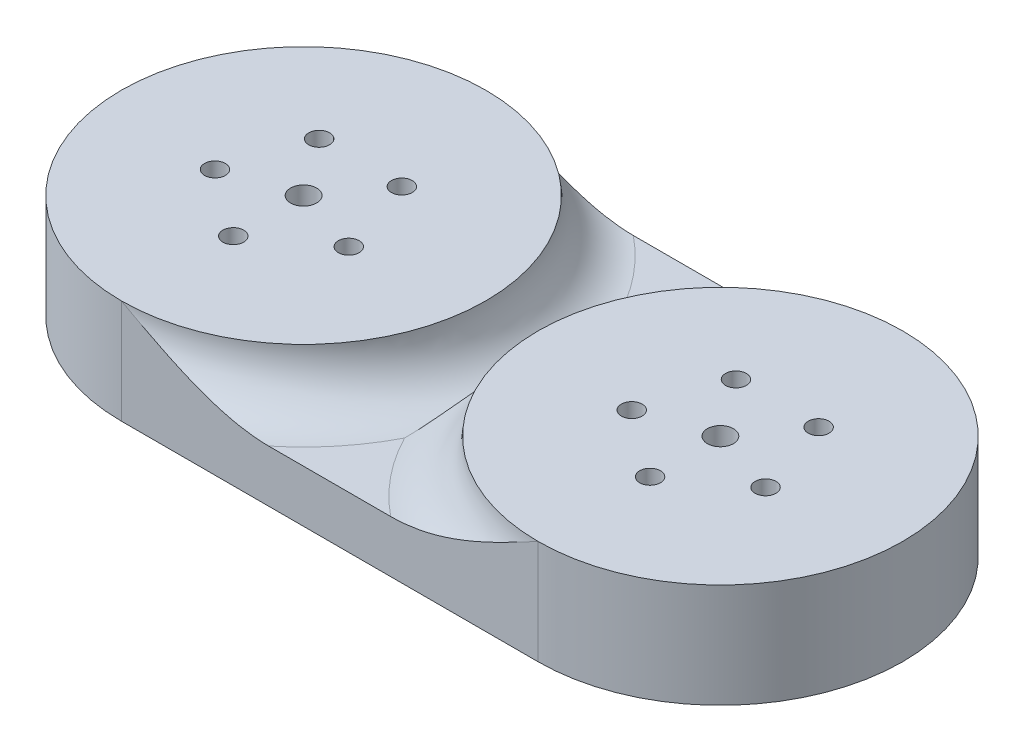
SolidWorks part; units mm, degrees
ref_plane "Front Plane" through (0, 0, 0) normal (0, 0, 1) x (1, 0, 0)
ref_plane "Top Plane" through (0, 0, 0) normal (0, 1, 0) x (1, 0, 0)
ref_plane "Right Plane" through (0, 0, 0) normal (1, 0, 0) x (0, 0, -1)
sketch "Sketch1" plane through (0, 0, 0) normal (0, 1, 0) x (1, 0, 0)
  circle A0 centre (0, 0) radius 35
  dimension "D1" = 70
extrude "Boss-Extrude1" add sketch "Sketch1" along normal blind 10
sketch "Sketch2" plane through (0, 0, 0) normal (0, -1, 0) x (1, 0, 0)
  circle A0 centre (0, 0) radius 13.5 construction
  circle A1 centre (0, 13.5) radius 2
  circle A2 centre (12.8393, 4.1717) radius 2
  circle A3 centre (7.9351, -10.9217) radius 2
  circle A4 centre (-7.9351, -10.9217) radius 2
  circle A5 centre (-12.8393, 4.1717) radius 2
  point P16 (0, 0)
  dimension "D1" = 27
  dimension "D2" = 4
extrude "Cut-Extrude1" cut sketch "Sketch2" against normal through all
sketch "Sketch3" plane through (0, 0, 0) normal (0, -1, 0) x (1, 0, 0)
  line L0 (0, 0) -> (80, 0) construction
  line L1 (80, 35) -> (0, 35)
  line L2 (80, -35) -> (0, -35)
  line L3 (40, 35) -> (40, -35) construction
  arc A0 (80, -35) -> (80, 35) centre (80, 0) ccw
  circle A1 centre (0, 0) radius 35 construction
  circle A2 centre (67.1607, 4.1717) radius 2
  circle A3 centre (0, 0) radius 35
  arc A4 (0, 35) -> (0, -35) centre (0, 0) ccw
  circle A5 centre (-12.8393, 4.1717) radius 2
  circle A6 centre (-12.8393, 4.1717) radius 2
  circle A7 centre (-7.9351, -10.9217) radius 2
  circle A8 centre (-7.9351, -10.9217) radius 2
  circle A9 centre (7.9351, -10.9217) radius 2
  circle A10 centre (7.9351, -10.9217) radius 2
  circle A11 centre (12.8393, 4.1717) radius 2
  circle A12 centre (12.8393, 4.1717) radius 2
  circle A13 centre (0, 13.5) radius 2
  circle A14 centre (0, 13.5) radius 2
  circle A15 centre (72.0649, -10.9217) radius 2
  circle A16 centre (87.9351, -10.9217) radius 2
  circle A17 centre (92.8393, 4.1717) radius 2
  circle A18 centre (80, 13.5) radius 2
  dimension "D1" = 80
  dimension "D2" = 0
  dimension "D3" = 0
  dimension "D4" = 0
  dimension "D5" = 0
  dimension "D6" = 0
  dimension "D7" = 0
extrude "Boss-Extrude2" add sketch "Sketch3" along normal blind 10
sketch "Sketch4" plane through (0, 0, 0) normal (0, 1, 0) x (1, 0, 0)
  circle A0 centre (80, 0) radius 35
  arc A1 (80, -35) -> (80, 35) centre (80, 0) ccw construction
  circle A2 centre (87.9351, 10.9217) radius 2 construction
  circle A3 centre (92.8393, -4.1717) radius 2 construction
  circle A4 centre (67.1607, -4.1717) radius 2 construction
  circle A5 centre (80, -13.5) radius 2 construction
  circle A6 centre (72.0649, 10.9217) radius 2 construction
  circle A7 centre (72.0649, 10.9217) radius 2
  circle A8 centre (80, -13.5) radius 2
  circle A9 centre (67.1607, -4.1717) radius 2
  circle A10 centre (92.8393, -4.1717) radius 2
  circle A11 centre (87.9351, 10.9217) radius 2
extrude "Boss-Extrude3" add sketch "Sketch4" along normal blind 10
fillet "Fillet1" radius 10 2 edges at (35, 0, 0) (45, 0, 0)
ref_plane "Plane1" through (80, 0, 0) normal (1, 0, 0) x (0, 0, -1)
ref_plane "Plane2" through (40, 0, 0) normal (1, 0, 0) x (0, 0, -1)
ref_axis "Axis1" through (40, -11.1361, 0) along (0, 1, 0)
ref_point "Point1"
sketch "Sketch5" plane through (0, -10, 0) normal (0, -1, 0) x (1, 0, 0)
  line L0 (80, -35) -> (80, 35) construction
  circle A0 centre (0, 0) radius 2.5
  circle A1 centre (80, 0) radius 2.5
  dimension "D1" = 5
extrude "Cut-Extrude2" cut sketch "Sketch5" against normal through all
